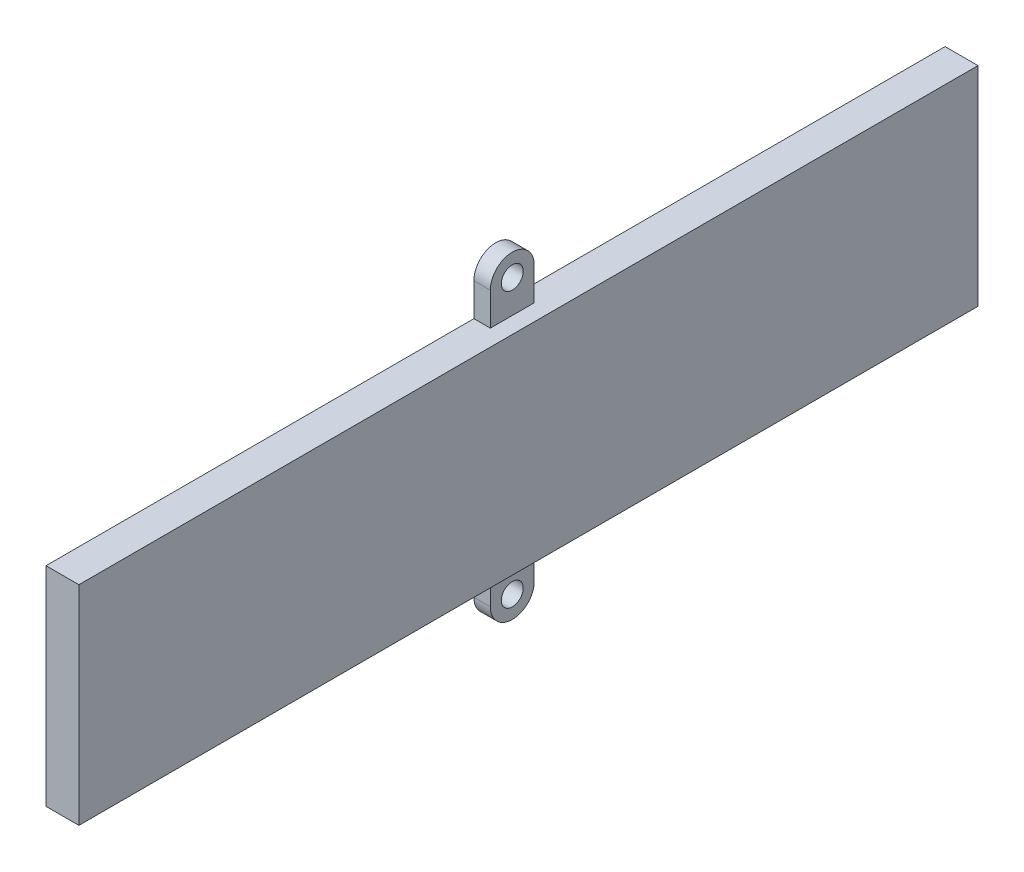
SolidWorks part; units mm, degrees
ref_plane "Alzado" through (0, 0, 0) normal (0, 0, 1) x (1, 0, 0)
ref_plane "Planta" through (0, 0, 0) normal (0, 1, 0) x (1, 0, 0)
ref_plane "Vista lateral" through (0, 0, 0) normal (1, 0, 0) x (0, 0, -1)
sketch "Croquis1" plane through (-42.2573, 0, 0) normal (-1, 0, 0) x (0, 0, 1)
  line L168 (50.1081, 25.9046) -> (54.1081, 25.9046)
  line L169 (50.1081, 6.9046) -> (54.1081, 6.9046)
  line L171 (11.1081, 25.9046) -> (93.1081, 25.9046)
  line L172 (11.1081, 25.9046) -> (11.1081, 6.9046)
  line L173 (11.1081, 6.9046) -> (93.1081, 6.9046)
  line L174 (93.1081, 25.9046) -> (93.1081, 6.9046)
  line L178 (54.1081, 6.9046) -> (54.1081, 3.9046)
  line L179 (50.1081, 3.9046) -> (50.1081, 6.9046)
  line L180 (93.1081, 6.9046) -> (54.1081, 6.9046)
  line L181 (93.1081, 25.9046) -> (93.1081, 6.9046)
  line L182 (54.1081, 25.9046) -> (93.1081, 25.9046)
  line L183 (54.1081, 28.9046) -> (54.1081, 25.9046)
  line L184 (50.1081, 25.9046) -> (50.1081, 28.9046)
  line L185 (11.1081, 25.9046) -> (50.1081, 25.9046)
  line L186 (11.1081, 6.9046) -> (11.1081, 25.9046)
  line L187 (50.1081, 6.9046) -> (11.1081, 6.9046)
  line L188 (54.1081, 6.9046) -> (54.1081, 3.9046)
  line L189 (50.1081, 3.9046) -> (50.1081, 6.9046)
  line L190 (93.1081, 6.9046) -> (54.1081, 6.9046)
  line L191 (93.1081, 25.9046) -> (93.1081, 6.9046)
  line L192 (54.1081, 25.9046) -> (93.1081, 25.9046)
  line L193 (54.1081, 28.9046) -> (54.1081, 25.9046)
  line L194 (50.1081, 25.9046) -> (50.1081, 28.9046)
  line L195 (11.1081, 25.9046) -> (50.1081, 25.9046)
  line L196 (11.1081, 6.9046) -> (11.1081, 25.9046)
  line L197 (50.1081, 6.9046) -> (11.1081, 6.9046)
  arc A28 (50.1081, 28.9046) -> (54.1081, 28.9046) centre (52.1081, 28.9046) cw
  arc A29 (50.1081, 3.9046) -> (54.1081, 3.9046) centre (52.1081, 3.9046) ccw
  arc A30 (50.1081, 3.9046) -> (54.1081, 3.9046) centre (52.1081, 3.9046) ccw
  dimension "D1" = 0.5
extrude "Saliente-Extruir1" add sketch "Croquis1" against normal up to surface (1.5 mm away) contours A28 L194 L168 L193 | L189 A30 L188 L169 region at (-42.2573, 28.2118, 52.1081) region at (-42.2573, 4.5974, 52.1081)
ref_plane "Plano1" through (-42.2573, 26.4046, 10.6081) normal (0, -1, 0) x (-1, 0, 0)
sketch "Croquis4" plane through (-42.2573, 0, 0) normal (-1, 0, 0) x (0, 0, 1)
  line L0 (10.6081, 26.4046) -> (49.6081, 26.4046) construction
  line L1 (11.1581, 25.9046) -> (93.1081, 25.9046)
  line L2 (11.1581, 25.9046) -> (11.1581, 6.9046)
  line L3 (11.1581, 6.9046) -> (93.1081, 6.9046)
  line L4 (93.1081, 25.9046) -> (93.1081, 6.9046)
  line L5 (54.6081, 6.4046) -> (93.6081, 6.4046) construction
  line L6 (10.6081, 26.4046) -> (10.6081, 6.4046) construction
  line L7 (93.6081, 26.4046) -> (93.6081, 6.4046) construction
  dimension "D1" = 0.5
  dimension "D2" = 0.5
  dimension "D3" = 0.55
  dimension "D4" = 0.5
extrude "Saliente-Extruir2" add sketch "Croquis4" against normal blind 3
sketch "Croquis5" plane through (-40.7573, 0, 0) normal (1, 0, 0) x (0, 0, -1)
  circle A0 centre (-52.1081, 28.9046) radius 1
  circle A1 centre (-52.1081, 3.9046) radius 1
extrude "Cortar-Extruir1" cut sketch "Croquis5" against normal blind 3
sketch "Croquis6" plane through (-42.2573, 0, 0) normal (-1, 0, 0) x (0, 0, 1)
  line L4 (27.972, 19.1109) -> (28.6141, 19.1109)
  line L5 (28.6141, 19.1109) -> (28.6141, 15.5831)
  line L6 (28.6141, 15.5831) -> (28.6225, 15.3461)
  line L7 (28.6225, 15.3461) -> (28.6477, 15.1286)
  line L8 (28.6477, 15.1286) -> (28.6666, 15.0269)
  line L9 (28.6666, 15.0269) -> (28.6896, 14.9299)
  line L10 (28.6896, 14.9299) -> (28.7167, 14.8374)
  line L11 (28.7167, 14.8374) -> (28.7479, 14.7495)
  line L12 (28.7479, 14.7495) -> (28.7832, 14.666)
  line L13 (28.7832, 14.666) -> (28.8225, 14.5868)
  line L14 (28.8225, 14.5868) -> (28.8659, 14.5119)
  line L15 (28.8659, 14.5119) -> (28.9133, 14.4412)
  line L16 (28.9133, 14.4412) -> (28.9646, 14.3747)
  line L17 (28.9646, 14.3747) -> (29.0199, 14.3123)
  line L18 (29.0199, 14.3123) -> (29.0792, 14.2538)
  line L19 (29.0792, 14.2538) -> (29.1424, 14.1993)
  line L20 (29.1424, 14.1993) -> (29.2095, 14.1486)
  line L21 (29.2095, 14.1486) -> (29.2805, 14.1018)
  line L22 (29.2805, 14.1018) -> (29.3553, 14.0586)
  line L23 (29.3553, 14.0586) -> (29.434, 14.0191)
  line L24 (29.434, 14.0191) -> (29.6029, 13.9507)
  line L25 (29.6029, 13.9507) -> (29.7868, 13.896)
  line L26 (29.7868, 13.896) -> (29.9857, 13.8545)
  line L27 (29.9857, 13.8545) -> (30.1994, 13.8255)
  line L28 (30.1994, 13.8255) -> (30.4277, 13.8086)
  line L29 (30.4277, 13.8086) -> (30.6704, 13.803)
  line L30 (30.6704, 13.803) -> (30.9971, 13.8117)
  line L31 (30.9971, 13.8117) -> (31.1455, 13.8225)
  line L32 (31.1455, 13.8225) -> (31.2845, 13.8374)
  line L33 (31.2845, 13.8374) -> (31.4145, 13.8565)
  line L34 (31.4145, 13.8565) -> (31.5359, 13.8797)
  line L35 (31.5359, 13.8797) -> (31.6491, 13.9069)
  line L36 (31.6491, 13.9069) -> (31.7546, 13.9381)
  line L37 (31.7546, 13.9381) -> (31.8527, 13.9732)
  line L38 (31.8527, 13.9732) -> (31.9439, 14.0121)
  line L39 (31.9439, 14.0121) -> (32.0287, 14.0549)
  line L40 (32.0287, 14.0549) -> (32.1073, 14.1013)
  line L41 (32.1073, 14.1013) -> (32.1803, 14.1514)
  line L42 (32.1803, 14.1514) -> (32.248, 14.2052)
  line L43 (32.248, 14.2052) -> (32.3109, 14.2625)
  line L44 (32.3109, 14.2625) -> (32.3694, 14.3233)
  line L45 (32.3694, 14.3233) -> (32.4198, 14.3825)
  line L46 (32.4198, 14.3825) -> (32.4647, 14.4442)
  line L47 (32.4647, 14.4442) -> (32.5043, 14.5082)
  line L48 (32.5043, 14.5082) -> (32.539, 14.5744)
  line L49 (32.539, 14.5744) -> (32.5947, 14.7123)
  line L50 (32.5947, 14.7123) -> (32.6346, 14.8567)
  line L51 (32.6346, 14.8567) -> (32.6611, 15.006)
  line L52 (32.6611, 15.006) -> (32.6769, 15.1588)
  line L53 (32.6769, 15.1588) -> (32.6844, 15.3138)
  line L54 (32.6844, 15.3138) -> (32.6864, 15.4694)
  line L55 (32.6864, 15.4694) -> (32.6864, 18.8101)
  line L56 (32.6864, 18.8101) -> (32.6895, 18.8697)
  line L57 (32.6895, 18.8697) -> (32.6995, 18.9257)
  line L58 (32.6995, 18.9257) -> (32.7168, 18.9767)
  line L59 (32.7168, 18.9767) -> (32.7422, 19.0215)
  line L60 (32.7422, 19.0215) -> (32.7765, 19.0586)
  line L61 (32.7765, 19.0586) -> (32.8201, 19.0868)
  line L62 (32.8201, 19.0868) -> (32.8739, 19.1046)
  line L63 (32.8739, 19.1046) -> (32.9384, 19.1109)
  line L64 (32.9384, 19.1109) -> (33.4261, 19.1109)
  line L65 (33.4261, 19.1109) -> (33.4261, 19.3548)
  line L66 (33.4261, 19.3548) -> (31.7108, 19.3548)
  line L67 (31.7108, 19.3548) -> (31.7108, 19.1109)
  line L68 (31.7108, 19.1109) -> (32.0766, 19.1109)
  line L69 (32.0766, 19.1109) -> (32.1601, 19.1046)
  line L70 (32.1601, 19.1046) -> (32.2333, 19.0868)
  line L71 (32.2333, 19.0868) -> (32.296, 19.0586)
  line L72 (32.296, 19.0586) -> (32.348, 19.0215)
  line L73 (32.348, 19.0215) -> (32.3889, 18.9767)
  line L74 (32.3889, 18.9767) -> (32.4184, 18.9257)
  line L75 (32.4184, 18.9257) -> (32.4364, 18.8697)
  line L76 (32.4364, 18.8697) -> (32.4424, 18.8101)
  line L77 (32.4424, 18.8101) -> (32.4424, 16.0791)
  line L78 (32.4424, 16.0791) -> (32.4395, 15.5927)
  line L79 (32.4395, 15.5927) -> (32.4326, 15.3665)
  line L80 (32.4326, 15.3665) -> (32.4191, 15.1574)
  line L81 (32.4191, 15.1574) -> (32.3968, 14.9702)
  line L82 (32.3968, 14.9702) -> (32.3636, 14.8091)
  line L83 (32.3636, 14.8091) -> (32.3422, 14.7397)
  line L84 (32.3422, 14.7397) -> (32.3173, 14.6786)
  line L85 (32.3173, 14.6786) -> (32.2885, 14.6263)
  line L86 (32.2885, 14.6263) -> (32.2556, 14.5834)
  line L87 (32.2556, 14.5834) -> (32.1826, 14.4923)
  line L88 (32.1826, 14.4923) -> (32.091, 14.3989)
  line L89 (32.091, 14.3989) -> (31.9796, 14.3078)
  line L90 (31.9796, 14.3078) -> (31.9161, 14.2646)
  line L91 (31.9161, 14.2646) -> (31.8472, 14.2236)
  line L92 (31.8472, 14.2236) -> (31.7728, 14.1855)
  line L93 (31.7728, 14.1855) -> (31.6927, 14.1509)
  line L94 (31.6927, 14.1509) -> (31.6068, 14.1202)
  line L95 (31.6068, 14.1202) -> (31.5149, 14.0941)
  line L96 (31.5149, 14.0941) -> (31.4169, 14.0732)
  line L97 (31.4169, 14.0732) -> (31.3127, 14.058)
  line L98 (31.3127, 14.058) -> (31.2021, 14.049)
  line L99 (31.2021, 14.049) -> (31.085, 14.047)
  line L100 (31.085, 14.047) -> (30.9212, 14.0528)
  line L101 (30.9212, 14.0528) -> (30.7738, 14.0672)
  line L102 (30.7738, 14.0672) -> (30.6419, 14.0901)
  line L103 (30.6419, 14.0901) -> (30.5248, 14.1217)
  line L104 (30.5248, 14.1217) -> (30.4217, 14.162)
  line L105 (30.4217, 14.162) -> (30.3316, 14.2108)
  line L106 (30.3316, 14.2108) -> (30.254, 14.2683)
  line L107 (30.254, 14.2683) -> (30.1879, 14.3344)
  line L108 (30.1879, 14.3344) -> (30.1326, 14.4093)
  line L109 (30.1326, 14.4093) -> (30.0872, 14.4928)
  line L110 (30.0872, 14.4928) -> (30.051, 14.5849)
  line L111 (30.051, 14.5849) -> (30.0231, 14.6858)
  line L112 (30.0231, 14.6858) -> (30.0029, 14.7954)
  line L113 (30.0029, 14.7954) -> (29.9894, 14.9138)
  line L114 (29.9894, 14.9138) -> (29.9819, 15.0408)
  line L115 (29.9819, 15.0408) -> (29.9796, 15.1767)
  line L116 (29.9796, 15.1767) -> (29.9796, 19.1109)
  line L117 (29.9796, 19.1109) -> (30.6623, 19.1109)
  line L118 (30.6623, 19.1109) -> (30.6623, 19.3548)
  line L119 (30.6623, 19.3548) -> (27.972, 19.3548)
  line L120 (27.972, 19.3548) -> (27.972, 19.1109)
  line L121 (19.4343, 21.6816) -> (22.1885, 18.3616)
  line L122 (22.1885, 18.3616) -> (22.3112, 18.1954)
  line L123 (22.3112, 18.1954) -> (22.4201, 18.0189)
  line L124 (22.4201, 18.0189) -> (22.5144, 17.833)
  line L125 (22.5144, 17.833) -> (22.5933, 17.6384)
  line L126 (22.5933, 17.6384) -> (22.6561, 17.4361)
  line L127 (22.6561, 17.4361) -> (22.7018, 17.2267)
  line L128 (22.7018, 17.2267) -> (22.7299, 17.0111)
  line L129 (22.7299, 17.0111) -> (22.737, 16.9012)
  line L130 (22.737, 16.9012) -> (22.7394, 16.79)
  line L131 (22.7394, 16.79) -> (22.7362, 16.6618)
  line L132 (22.7362, 16.6618) -> (22.7266, 16.5352)
  line L133 (22.7266, 16.5352) -> (22.7109, 16.4104)
  line L134 (22.7109, 16.4104) -> (22.6892, 16.2877)
  line L135 (22.6892, 16.2877) -> (22.6617, 16.167)
  line L136 (22.6617, 16.167) -> (22.6284, 16.0488)
  line L137 (22.6284, 16.0488) -> (22.5896, 15.9329)
  line L138 (22.5896, 15.9329) -> (22.5454, 15.8197)
  line L139 (22.5454, 15.8197) -> (22.496, 15.7093)
  line L140 (22.496, 15.7093) -> (22.4415, 15.6018)
  line L141 (22.4415, 15.6018) -> (22.3821, 15.4974)
  line L142 (22.3821, 15.4974) -> (22.3179, 15.3962)
  line L143 (22.3179, 15.3962) -> (22.2491, 15.2985)
  line L144 (22.2491, 15.2985) -> (22.1758, 15.2043)
  line L145 (22.1758, 15.2043) -> (22.0982, 15.1139)
  line L146 (22.0982, 15.1139) -> (22.0165, 15.0273)
  line L147 (22.0165, 15.0273) -> (21.9308, 14.9447)
  line L148 (21.9308, 14.9447) -> (21.8412, 14.8664)
  line L149 (21.8412, 14.8664) -> (21.748, 14.7923)
  line L150 (21.748, 14.7923) -> (21.6512, 14.7228)
  line L151 (21.6512, 14.7228) -> (21.551, 14.658)
  line L152 (21.551, 14.658) -> (21.4477, 14.5979)
  line L153 (21.4477, 14.5979) -> (21.3412, 14.5429)
  line L154 (21.3412, 14.5429) -> (21.2319, 14.493)
  line L155 (21.2319, 14.493) -> (21.1198, 14.4483)
  line L156 (21.1198, 14.4483) -> (21.0051, 14.4091)
  line L157 (21.0051, 14.4091) -> (20.888, 14.3755)
  line L158 (20.888, 14.3755) -> (20.7686, 14.3477)
  line L159 (20.7686, 14.3477) -> (20.647, 14.3257)
  line L160 (20.647, 14.3257) -> (20.5235, 14.3099)
  line L161 (20.5235, 14.3099) -> (20.3981, 14.3003)
  line L162 (20.3981, 14.3003) -> (20.2711, 14.297)
  line L163 (20.2711, 14.297) -> (20.1077, 14.3027)
  line L164 (20.1077, 14.3027) -> (19.9476, 14.3196)
  line L165 (19.9476, 14.3196) -> (19.7911, 14.3471)
  line L166 (19.7911, 14.3471) -> (19.6385, 14.3849)
  line L167 (19.6385, 14.3849) -> (19.4898, 14.4323)
  line L168 (19.4898, 14.4323) -> (19.3454, 14.4891)
  line L169 (19.3454, 14.4891) -> (19.2054, 14.5546)
  line L170 (19.2054, 14.5546) -> (19.0701, 14.6284)
  line L171 (19.0701, 14.6284) -> (18.9396, 14.7101)
  line L172 (18.9396, 14.7101) -> (18.8143, 14.7992)
  line L173 (18.8143, 14.7992) -> (18.6942, 14.8952)
  line L174 (18.6942, 14.8952) -> (18.5797, 14.9976)
  line L175 (18.5797, 14.9976) -> (18.471, 15.106)
  line L176 (18.471, 15.106) -> (18.3682, 15.2199)
  line L177 (18.3682, 15.2199) -> (18.2716, 15.3388)
  line L178 (18.2716, 15.3388) -> (18.1814, 15.4624)
  line L179 (18.1814, 15.4624) -> (16.7124, 17.2468)
  line L180 (16.7124, 17.2468) -> (16.7124, 18.0118)
  line L181 (16.7124, 18.0118) -> (18.5461, 15.7244)
  line L182 (18.5461, 15.7244) -> (18.5617, 15.6995)
  line L183 (18.5617, 15.6995) -> (18.7273, 15.5167)
  line L184 (18.7273, 15.5167) -> (18.9066, 15.3421)
  line L185 (18.9066, 15.3421) -> (19.0013, 15.2594)
  line L186 (19.0013, 15.2594) -> (19.0995, 15.1806)
  line L187 (19.0995, 15.1806) -> (19.2011, 15.1063)
  line L188 (19.2011, 15.1063) -> (19.3061, 15.0372)
  line L189 (19.3061, 15.0372) -> (19.4146, 14.9739)
  line L190 (19.4146, 14.9739) -> (19.5265, 14.917)
  line L191 (19.5265, 14.917) -> (19.6419, 14.8671)
  line L192 (19.6419, 14.8671) -> (19.7608, 14.8249)
  line L193 (19.7608, 14.8249) -> (19.8831, 14.791)
  line L194 (19.8831, 14.791) -> (20.0089, 14.766)
  line L195 (20.0089, 14.766) -> (20.1382, 14.7506)
  line L196 (20.1382, 14.7506) -> (20.2711, 14.7453)
  line L197 (20.2711, 14.7453) -> (20.3747, 14.7479)
  line L198 (20.3747, 14.7479) -> (20.4769, 14.7558)
  line L199 (20.4769, 14.7558) -> (20.5778, 14.7687)
  line L200 (20.5778, 14.7687) -> (20.677, 14.7866)
  line L201 (20.677, 14.7866) -> (20.7745, 14.8094)
  line L202 (20.7745, 14.8094) -> (20.8703, 14.8368)
  line L203 (20.8703, 14.8368) -> (20.964, 14.8689)
  line L204 (20.964, 14.8689) -> (21.0557, 14.9054)
  line L205 (21.0557, 14.9054) -> (21.1451, 14.9462)
  line L206 (21.1451, 14.9462) -> (21.2322, 14.9912)
  line L207 (21.2322, 14.9912) -> (21.3988, 15.0934)
  line L208 (21.3988, 15.0934) -> (21.5544, 15.2109)
  line L209 (21.5544, 15.2109) -> (21.698, 15.3426)
  line L210 (21.698, 15.3426) -> (21.8286, 15.4877)
  line L211 (21.8286, 15.4877) -> (21.9452, 15.645)
  line L212 (21.9452, 15.645) -> (22.0467, 15.8135)
  line L213 (22.0467, 15.8135) -> (22.0914, 15.9017)
  line L214 (22.0914, 15.9017) -> (22.132, 15.9924)
  line L215 (22.132, 15.9924) -> (22.1683, 16.0853)
  line L216 (22.1683, 16.0853) -> (22.2002, 16.1804)
  line L217 (22.2002, 16.1804) -> (22.2275, 16.2776)
  line L218 (22.2275, 16.2776) -> (22.2501, 16.3768)
  line L219 (22.2501, 16.3768) -> (22.268, 16.4777)
  line L220 (22.268, 16.4777) -> (22.2809, 16.5803)
  line L221 (22.2809, 16.5803) -> (22.2887, 16.6844)
  line L222 (22.2887, 16.6844) -> (22.2914, 16.79)
  line L223 (22.2914, 16.79) -> (22.2836, 16.9709)
  line L224 (22.2836, 16.9709) -> (22.2608, 17.1473)
  line L225 (22.2608, 17.1473) -> (22.2236, 17.3185)
  line L226 (22.2236, 17.3185) -> (22.1726, 17.4839)
  line L227 (22.1726, 17.4839) -> (22.1085, 17.6429)
  line L228 (22.1085, 17.6429) -> (22.032, 17.7947)
  line L229 (22.032, 17.7947) -> (21.9437, 17.9389)
  line L230 (21.9437, 17.9389) -> (21.8442, 18.0746)
  line L231 (21.8442, 18.0746) -> (19.4343, 20.9137)
  line L232 (19.4343, 20.9137) -> (19.4343, 21.6816)
  line L233 (21.6493, 17.6288) -> (21.6993, 17.5345)
  line L234 (21.6993, 17.5345) -> (21.7428, 17.4363)
  line L235 (21.7428, 17.4363) -> (21.7799, 17.3346)
  line L236 (21.7799, 17.3346) -> (21.8104, 17.2295)
  line L237 (21.8104, 17.2295) -> (21.8343, 17.1216)
  line L238 (21.8343, 17.1216) -> (21.8514, 17.0112)
  line L239 (21.8514, 17.0112) -> (21.8617, 16.8987)
  line L240 (21.8617, 16.8987) -> (21.8652, 16.7843)
  line L241 (21.8652, 16.7843) -> (21.857, 16.6167)
  line L242 (21.857, 16.6167) -> (21.833, 16.4538)
  line L243 (21.833, 16.4538) -> (21.794, 16.2967)
  line L244 (21.794, 16.2967) -> (21.7408, 16.146)
  line L245 (21.7408, 16.146) -> (21.6741, 16.0026)
  line L246 (21.6741, 16.0026) -> (21.5948, 15.8674)
  line L247 (21.5948, 15.8674) -> (21.5037, 15.7411)
  line L248 (21.5037, 15.7411) -> (21.4015, 15.6247)
  line L249 (21.4015, 15.6247) -> (21.2891, 15.5188)
  line L250 (21.2891, 15.5188) -> (21.1672, 15.4244)
  line L251 (21.1672, 15.4244) -> (21.0367, 15.3422)
  line L252 (21.0367, 15.3422) -> (20.8983, 15.2732)
  line L253 (20.8983, 15.2732) -> (20.7528, 15.218)
  line L254 (20.7528, 15.218) -> (20.6011, 15.1776)
  line L255 (20.6011, 15.1776) -> (20.4439, 15.1527)
  line L256 (20.4439, 15.1527) -> (20.282, 15.1443)
  line L257 (20.282, 15.1443) -> (20.1805, 15.1476)
  line L258 (20.1805, 15.1476) -> (20.0807, 15.1574)
  line L259 (20.0807, 15.1574) -> (19.9828, 15.1735)
  line L260 (19.9828, 15.1735) -> (19.887, 15.1957)
  line L261 (19.887, 15.1957) -> (19.7934, 15.2238)
  line L262 (19.7934, 15.2238) -> (19.7024, 15.2577)
  line L263 (19.7024, 15.2577) -> (19.614, 15.297)
  line L264 (19.614, 15.297) -> (19.5285, 15.3416)
  line L265 (19.5285, 15.3416) -> (19.446, 15.3913)
  line L266 (19.446, 15.3913) -> (19.3668, 15.4459)
  line L267 (19.3668, 15.4459) -> (19.2911, 15.5052)
  line L268 (19.2911, 15.5052) -> (19.219, 15.569)
  line L269 (19.219, 15.569) -> (19.1507, 15.6371)
  line L270 (19.1507, 15.6371) -> (19.0864, 15.7093)
  line L271 (19.0864, 15.7093) -> (19.0264, 15.7853)
  line L272 (19.0264, 15.7853) -> (18.9707, 15.8651)
  line L273 (18.9707, 15.8651) -> (16.7124, 18.6246)
  line L274 (16.7124, 18.6246) -> (16.7124, 19.3898)
  line L275 (16.7124, 19.3898) -> (19.4043, 16.097)
  line L276 (19.4043, 16.097) -> (19.4931, 15.982)
  line L277 (19.4931, 15.982) -> (19.5807, 15.8903)
  line L278 (19.5807, 15.8903) -> (19.6703, 15.8185)
  line L279 (19.6703, 15.8185) -> (19.7653, 15.7633)
  line L280 (19.7653, 15.7633) -> (19.8687, 15.7212)
  line L281 (19.8687, 15.7212) -> (19.9838, 15.6889)
  line L282 (19.9838, 15.6889) -> (20.1139, 15.663)
  line L283 (20.1139, 15.663) -> (20.2621, 15.6402)
  line L284 (20.2621, 15.6402) -> (20.3759, 15.6319)
  line L285 (20.3759, 15.6319) -> (20.4867, 15.639)
  line L286 (20.4867, 15.639) -> (20.5938, 15.6604)
  line L287 (20.5938, 15.6604) -> (20.6966, 15.6954)
  line L288 (20.6966, 15.6954) -> (20.7946, 15.7427)
  line L289 (20.7946, 15.7427) -> (20.8873, 15.8016)
  line L290 (20.8873, 15.8016) -> (20.9738, 15.8711)
  line L291 (20.9738, 15.8711) -> (21.0538, 15.95)
  line L292 (21.0538, 15.95) -> (21.1266, 16.0376)
  line L293 (21.1266, 16.0376) -> (21.1916, 16.1328)
  line L294 (21.1916, 16.1328) -> (21.2483, 16.2346)
  line L295 (21.2483, 16.2346) -> (21.2959, 16.3421)
  line L296 (21.2959, 16.3421) -> (21.334, 16.4543)
  line L297 (21.334, 16.4543) -> (21.362, 16.5703)
  line L298 (21.362, 16.5703) -> (21.3792, 16.689)
  line L299 (21.3792, 16.689) -> (21.385, 16.8095)
  line L300 (21.385, 16.8095) -> (21.3806, 16.9614)
  line L301 (21.3806, 16.9614) -> (21.3639, 17.1041)
  line L302 (21.3639, 17.1041) -> (21.3494, 17.1726)
  line L303 (21.3494, 17.1726) -> (21.3299, 17.2394)
  line L304 (21.3299, 17.2394) -> (21.3048, 17.3048)
  line L305 (21.3048, 17.3048) -> (21.2734, 17.3691)
  line L306 (21.2734, 17.3691) -> (19.4343, 19.5605)
  line L307 (19.4343, 19.5605) -> (19.4343, 20.3283)
  line L308 (19.4343, 20.3283) -> (21.6493, 17.6288)
  line L309 (20.8854, 17.2656) -> (20.9267, 16.9801)
  line L310 (20.9267, 16.9801) -> (20.8442, 16.5564)
  line L311 (20.8442, 16.5564) -> (20.7935, 16.3357)
  line L312 (20.7935, 16.3357) -> (20.7507, 16.1815)
  line L313 (20.7507, 16.1815) -> (20.7306, 16.1274)
  line L314 (20.7306, 16.1274) -> (20.7134, 16.1016)
  line L315 (20.7134, 16.1016) -> (20.609, 16.0515)
  line L316 (20.609, 16.0515) -> (20.509, 16.0175)
  line L317 (20.509, 16.0175) -> (20.4138, 15.998)
  line L318 (20.4138, 15.998) -> (20.3236, 15.991)
  line L319 (20.3236, 15.991) -> (20.2388, 15.9949)
  line L320 (20.2388, 15.9949) -> (20.1596, 16.0078)
  line L321 (20.1596, 16.0078) -> (20.0864, 16.0279)
  line L322 (20.0864, 16.0279) -> (20.0195, 16.0535)
  line L323 (20.0195, 16.0535) -> (19.9055, 16.114)
  line L324 (19.9055, 16.114) -> (19.8201, 16.175)
  line L325 (19.8201, 16.175) -> (19.7656, 16.2223)
  line L326 (19.7656, 16.2223) -> (19.7445, 16.2416)
  line L327 (19.7445, 16.2416) -> (19.813, 16.1997)
  line L328 (19.813, 16.1997) -> (19.8875, 16.1685)
  line L329 (19.8875, 16.1685) -> (19.9671, 16.149)
  line L330 (19.9671, 16.149) -> (20.0508, 16.1423)
  line L331 (20.0508, 16.1423) -> (20.1054, 16.1451)
  line L332 (20.1054, 16.1451) -> (20.1585, 16.1534)
  line L333 (20.1585, 16.1534) -> (20.2097, 16.167)
  line L334 (20.2097, 16.167) -> (20.2587, 16.1855)
  line L335 (20.2587, 16.1855) -> (20.3054, 16.2087)
  line L336 (20.3054, 16.2087) -> (20.3495, 16.2362)
  line L337 (20.3495, 16.2362) -> (20.3906, 16.2679)
  line L338 (20.3906, 16.2679) -> (20.4285, 16.3034)
  line L339 (20.4285, 16.3034) -> (20.463, 16.3425)
  line L340 (20.463, 16.3425) -> (20.4938, 16.3848)
  line L341 (20.4938, 16.3848) -> (20.5205, 16.4302)
  line L342 (20.5205, 16.4302) -> (20.543, 16.4783)
  line L343 (20.543, 16.4783) -> (20.561, 16.5289)
  line L344 (20.561, 16.5289) -> (20.5741, 16.5816)
  line L345 (20.5741, 16.5816) -> (20.5822, 16.6362)
  line L346 (20.5822, 16.6362) -> (20.585, 16.6925)
  line L347 (20.585, 16.6925) -> (20.5825, 16.7455)
  line L348 (20.5825, 16.7455) -> (20.5753, 16.797)
  line L349 (20.5753, 16.797) -> (20.5475, 16.8947)
  line L350 (20.5475, 16.8947) -> (20.5033, 16.984)
  line L351 (20.5033, 16.984) -> (20.4445, 17.0631)
  line L352 (20.4445, 17.0631) -> (19.4343, 18.2593)
  line L353 (19.4343, 18.2593) -> (19.4343, 19.0269)
  line L354 (19.4343, 19.0269) -> (20.8854, 17.2656)
  line L355 (17.829, 14.5352) -> (16.7124, 15.8936)
  line L356 (16.7124, 15.8936) -> (16.7124, 16.6586)
  line L357 (16.7124, 16.6586) -> (17.985, 15.071)
  line L358 (17.985, 15.071) -> (18.0605, 14.9833)
  line L359 (18.0605, 14.9833) -> (18.1436, 14.8877)
  line L360 (18.1436, 14.8877) -> (18.2566, 14.7682)
  line L361 (18.2566, 14.7682) -> (18.399, 14.6326)
  line L362 (18.399, 14.6326) -> (18.5705, 14.4891)
  line L363 (18.5705, 14.4891) -> (18.6671, 14.4168)
  line L364 (18.6671, 14.4168) -> (18.7709, 14.3454)
  line L365 (18.7709, 14.3454) -> (18.8817, 14.2761)
  line L366 (18.8817, 14.2761) -> (18.9997, 14.2097)
  line L367 (18.9997, 14.2097) -> (19.1247, 14.1473)
  line L368 (19.1247, 14.1473) -> (19.2567, 14.0898)
  line L369 (19.2567, 14.0898) -> (19.3956, 14.0383)
  line L370 (19.3956, 14.0383) -> (19.5415, 13.9938)
  line L371 (19.5415, 13.9938) -> (19.6942, 13.9571)
  line L372 (19.6942, 13.9571) -> (19.8537, 13.9294)
  line L373 (19.8537, 13.9294) -> (20.0201, 13.9117)
  line L374 (20.0201, 13.9117) -> (20.1932, 13.9048)
  line L375 (20.1932, 13.9048) -> (20.373, 13.9099)
  line L376 (20.373, 13.9099) -> (20.5594, 13.9279)
  line L377 (20.5594, 13.9279) -> (20.7525, 13.9598)
  line L378 (20.7525, 13.9598) -> (20.9521, 14.0066)
  line L379 (20.9521, 14.0066) -> (21.1583, 14.0693)
  line L380 (21.1583, 14.0693) -> (21.371, 14.1488)
  line L381 (21.371, 14.1488) -> (21.5902, 14.2463)
  line L382 (21.5902, 14.2463) -> (21.8157, 14.3626)
  line L383 (21.8157, 14.3626) -> (21.7398, 14.2879)
  line L384 (21.7398, 14.2879) -> (21.6565, 14.2156)
  line L385 (21.6565, 14.2156) -> (21.5659, 14.146)
  line L386 (21.5659, 14.146) -> (21.4686, 14.0793)
  line L387 (21.4686, 14.0793) -> (21.365, 14.0161)
  line L388 (21.365, 14.0161) -> (21.2553, 13.9566)
  line L389 (21.2553, 13.9566) -> (21.14, 13.9011)
  line L390 (21.14, 13.9011) -> (21.0194, 13.85)
  line L391 (21.0194, 13.85) -> (20.8939, 13.8037)
  line L392 (20.8939, 13.8037) -> (20.7639, 13.7624)
  line L393 (20.7639, 13.7624) -> (20.6297, 13.7266)
  line L394 (20.6297, 13.7266) -> (20.4917, 13.6965)
  line L395 (20.4917, 13.6965) -> (20.3503, 13.6725)
  line L396 (20.3503, 13.6725) -> (20.2059, 13.6549)
  line L397 (20.2059, 13.6549) -> (20.0588, 13.6442)
  line L398 (20.0588, 13.6442) -> (19.9095, 13.6405)
  line L399 (19.9095, 13.6405) -> (19.734, 13.6456)
  line L400 (19.734, 13.6456) -> (19.563, 13.6606)
  line L401 (19.563, 13.6606) -> (19.3967, 13.6847)
  line L402 (19.3967, 13.6847) -> (19.2355, 13.7173)
  line L403 (19.2355, 13.7173) -> (19.0798, 13.7578)
  line L404 (19.0798, 13.7578) -> (18.9299, 13.8055)
  line L405 (18.9299, 13.8055) -> (18.7862, 13.8597)
  line L406 (18.7862, 13.8597) -> (18.649, 13.9199)
  line L407 (18.649, 13.9199) -> (18.5187, 13.9853)
  line L408 (18.5187, 13.9853) -> (18.3957, 14.0552)
  line L409 (18.3957, 14.0552) -> (18.2802, 14.1292)
  line L410 (18.2802, 14.1292) -> (18.1727, 14.2064)
  line L411 (18.1727, 14.2064) -> (18.0734, 14.2863)
  line L412 (18.0734, 14.2863) -> (17.9828, 14.3682)
  line L413 (17.9828, 14.3682) -> (17.9012, 14.4514)
  line L414 (17.9012, 14.4514) -> (17.829, 14.5352)
  line L415 (23.8929, 21.6816) -> (21.1385, 18.3616)
  line L416 (21.1385, 18.3616) -> (21.0157, 18.1954)
  line L417 (21.0157, 18.1954) -> (20.9068, 18.0189)
  line L418 (20.9068, 18.0189) -> (20.8126, 17.833)
  line L419 (20.8126, 17.833) -> (20.7337, 17.6384)
  line L420 (20.7337, 17.6384) -> (20.6709, 17.4361)
  line L421 (20.6709, 17.4361) -> (20.6252, 17.2267)
  line L422 (20.6252, 17.2267) -> (20.5971, 17.0111)
  line L423 (20.5971, 17.0111) -> (20.59, 16.9012)
  line L424 (20.59, 16.9012) -> (20.5876, 16.79)
  line L425 (20.5876, 16.79) -> (20.5908, 16.6618)
  line L426 (20.5908, 16.6618) -> (20.6004, 16.5352)
  line L427 (20.6004, 16.5352) -> (20.6161, 16.4104)
  line L428 (20.6161, 16.4104) -> (20.6378, 16.2877)
  line L429 (20.6378, 16.2877) -> (20.6653, 16.167)
  line L430 (20.6653, 16.167) -> (20.6986, 16.0488)
  line L431 (20.6986, 16.0488) -> (20.7374, 15.9329)
  line L432 (20.7374, 15.9329) -> (20.7816, 15.8197)
  line L433 (20.7816, 15.8197) -> (20.831, 15.7093)
  line L434 (20.831, 15.7093) -> (20.8856, 15.6018)
  line L435 (20.8856, 15.6018) -> (20.945, 15.4974)
  line L436 (20.945, 15.4974) -> (21.0092, 15.3962)
  line L437 (21.0092, 15.3962) -> (21.078, 15.2985)
  line L438 (21.078, 15.2985) -> (21.1513, 15.2043)
  line L439 (21.1513, 15.2043) -> (21.2289, 15.1139)
  line L440 (21.2289, 15.1139) -> (21.3106, 15.0273)
  line L441 (21.3106, 15.0273) -> (21.3964, 14.9447)
  line L442 (21.3964, 14.9447) -> (21.4859, 14.8664)
  line L443 (21.4859, 14.8664) -> (21.5792, 14.7923)
  line L444 (21.5792, 14.7923) -> (21.676, 14.7228)
  line L445 (21.676, 14.7228) -> (21.7761, 14.658)
  line L446 (21.7761, 14.658) -> (21.8795, 14.5979)
  line L447 (21.8795, 14.5979) -> (21.9859, 14.5429)
  line L448 (21.9859, 14.5429) -> (22.0953, 14.493)
  line L449 (22.0953, 14.493) -> (22.2074, 14.4483)
  line L450 (22.2074, 14.4483) -> (22.3221, 14.4091)
  line L451 (22.3221, 14.4091) -> (22.4392, 14.3755)
  line L452 (22.4392, 14.3755) -> (22.5586, 14.3477)
  line L453 (22.5586, 14.3477) -> (22.6802, 14.3257)
  line L454 (22.6802, 14.3257) -> (22.8037, 14.3099)
  line L455 (22.8037, 14.3099) -> (22.9291, 14.3003)
  line L456 (22.9291, 14.3003) -> (23.0561, 14.297)
  line L457 (23.0561, 14.297) -> (23.2195, 14.3027)
  line L458 (23.2195, 14.3027) -> (23.3795, 14.3196)
  line L459 (23.3795, 14.3196) -> (23.536, 14.3471)
  line L460 (23.536, 14.3471) -> (23.6886, 14.3849)
  line L461 (23.6886, 14.3849) -> (23.8373, 14.4323)
  line L462 (23.8373, 14.4323) -> (23.9817, 14.4891)
  line L463 (23.9817, 14.4891) -> (24.1217, 14.5546)
  line L464 (24.1217, 14.5546) -> (24.257, 14.6284)
  line L465 (24.257, 14.6284) -> (24.3874, 14.7101)
  line L466 (24.3874, 14.7101) -> (24.5127, 14.7992)
  line L467 (24.5127, 14.7992) -> (24.6328, 14.8952)
  line L468 (24.6328, 14.8952) -> (24.7473, 14.9976)
  line L469 (24.7473, 14.9976) -> (24.856, 15.106)
  line L470 (24.856, 15.106) -> (24.9588, 15.2199)
  line L471 (24.9588, 15.2199) -> (25.0554, 15.3388)
  line L472 (25.0554, 15.3388) -> (25.1456, 15.4624)
  line L473 (25.1456, 15.4624) -> (26.6146, 17.2468)
  line L474 (26.6146, 17.2468) -> (26.6146, 18.0118)
  line L475 (26.6146, 18.0118) -> (24.7809, 15.7244)
  line L476 (24.7809, 15.7244) -> (24.7656, 15.6995)
  line L477 (24.7656, 15.6995) -> (24.5998, 15.5167)
  line L478 (24.5998, 15.5167) -> (24.4205, 15.3421)
  line L479 (24.4205, 15.3421) -> (24.3258, 15.2594)
  line L480 (24.3258, 15.2594) -> (24.2276, 15.1806)
  line L481 (24.2276, 15.1806) -> (24.126, 15.1063)
  line L482 (24.126, 15.1063) -> (24.0209, 15.0372)
  line L483 (24.0209, 15.0372) -> (23.9125, 14.9739)
  line L484 (23.9125, 14.9739) -> (23.8006, 14.917)
  line L485 (23.8006, 14.917) -> (23.6852, 14.8671)
  line L486 (23.6852, 14.8671) -> (23.5663, 14.8249)
  line L487 (23.5663, 14.8249) -> (23.444, 14.791)
  line L488 (23.444, 14.791) -> (23.3182, 14.766)
  line L489 (23.3182, 14.766) -> (23.1889, 14.7506)
  line L490 (23.1889, 14.7506) -> (23.0561, 14.7453)
  line L491 (23.0561, 14.7453) -> (22.9525, 14.7479)
  line L492 (22.9525, 14.7479) -> (22.8502, 14.7558)
  line L493 (22.8502, 14.7558) -> (22.7494, 14.7687)
  line L494 (22.7494, 14.7687) -> (22.6501, 14.7866)
  line L495 (22.6501, 14.7866) -> (22.5526, 14.8094)
  line L496 (22.5526, 14.8094) -> (22.4568, 14.8368)
  line L497 (22.4568, 14.8368) -> (22.3631, 14.8689)
  line L498 (22.3631, 14.8689) -> (22.2714, 14.9054)
  line L499 (22.2714, 14.9054) -> (22.182, 14.9462)
  line L500 (22.182, 14.9462) -> (22.0949, 14.9912)
  line L501 (22.0949, 14.9912) -> (21.9283, 15.0934)
  line L502 (21.9283, 15.0934) -> (21.7726, 15.2109)
  line L503 (21.7726, 15.2109) -> (21.629, 15.3426)
  line L504 (21.629, 15.3426) -> (21.4984, 15.4877)
  line L505 (21.4984, 15.4877) -> (21.3818, 15.645)
  line L506 (21.3818, 15.645) -> (21.2803, 15.8135)
  line L507 (21.2803, 15.8135) -> (21.2356, 15.9017)
  line L508 (21.2356, 15.9017) -> (21.195, 15.9924)
  line L509 (21.195, 15.9924) -> (21.1587, 16.0853)
  line L510 (21.1587, 16.0853) -> (21.1268, 16.1804)
  line L511 (21.1268, 16.1804) -> (21.0995, 16.2776)
  line L512 (21.0995, 16.2776) -> (21.0769, 16.3768)
  line L513 (21.0769, 16.3768) -> (21.059, 16.4777)
  line L514 (21.059, 16.4777) -> (21.0461, 16.5803)
  line L515 (21.0461, 16.5803) -> (21.0383, 16.6844)
  line L516 (21.0383, 16.6844) -> (21.0356, 16.79)
  line L517 (21.0356, 16.79) -> (21.0434, 16.9709)
  line L518 (21.0434, 16.9709) -> (21.0662, 17.1473)
  line L519 (21.0662, 17.1473) -> (21.1034, 17.3185)
  line L520 (21.1034, 17.3185) -> (21.1544, 17.4839)
  line L521 (21.1544, 17.4839) -> (21.2184, 17.6429)
  line L522 (21.2184, 17.6429) -> (21.295, 17.7947)
  line L523 (21.295, 17.7947) -> (21.3833, 17.9389)
  line L524 (21.3833, 17.9389) -> (21.4828, 18.0746)
  line L525 (21.4828, 18.0746) -> (23.8929, 20.9137)
  line L526 (23.8929, 20.9137) -> (23.8929, 21.6816)
  line L527 (21.6777, 17.6288) -> (21.6278, 17.5345)
  line L528 (21.6278, 17.5345) -> (21.5843, 17.4363)
  line L529 (21.5843, 17.4363) -> (21.5472, 17.3346)
  line L530 (21.5472, 17.3346) -> (21.5167, 17.2295)
  line L531 (21.5167, 17.2295) -> (21.4928, 17.1216)
  line L532 (21.4928, 17.1216) -> (21.4756, 17.0112)
  line L533 (21.4756, 17.0112) -> (21.4653, 16.8987)
  line L534 (21.4653, 16.8987) -> (21.4618, 16.7843)
  line L535 (21.4618, 16.7843) -> (21.47, 16.6167)
  line L536 (21.47, 16.6167) -> (21.4939, 16.4538)
  line L537 (21.4939, 16.4538) -> (21.533, 16.2967)
  line L538 (21.533, 16.2967) -> (21.5862, 16.146)
  line L539 (21.5862, 16.146) -> (21.6529, 16.0026)
  line L540 (21.6529, 16.0026) -> (21.7322, 15.8674)
  line L541 (21.7322, 15.8674) -> (21.8233, 15.7411)
  line L542 (21.8233, 15.7411) -> (21.9255, 15.6247)
  line L543 (21.9255, 15.6247) -> (22.0379, 15.5188)
  line L544 (22.0379, 15.5188) -> (22.1598, 15.4244)
  line L545 (22.1598, 15.4244) -> (22.2903, 15.3422)
  line L546 (22.2903, 15.3422) -> (22.4287, 15.2732)
  line L547 (22.4287, 15.2732) -> (22.5742, 15.218)
  line L548 (22.5742, 15.218) -> (22.7259, 15.1776)
  line L549 (22.7259, 15.1776) -> (22.8831, 15.1527)
  line L550 (22.8831, 15.1527) -> (23.045, 15.1443)
  line L551 (23.045, 15.1443) -> (23.1465, 15.1476)
  line L552 (23.1465, 15.1476) -> (23.2463, 15.1574)
  line L553 (23.2463, 15.1574) -> (23.3442, 15.1735)
  line L554 (23.3442, 15.1735) -> (23.44, 15.1957)
  line L555 (23.44, 15.1957) -> (23.5335, 15.2238)
  line L556 (23.5335, 15.2238) -> (23.6246, 15.2577)
  line L557 (23.6246, 15.2577) -> (23.713, 15.297)
  line L558 (23.713, 15.297) -> (23.7985, 15.3416)
  line L559 (23.7985, 15.3416) -> (23.8809, 15.3913)
  line L560 (23.8809, 15.3913) -> (23.9601, 15.4459)
  line L561 (23.9601, 15.4459) -> (24.0359, 15.5052)
  line L562 (24.0359, 15.5052) -> (24.108, 15.569)
  line L563 (24.108, 15.569) -> (24.1763, 15.6371)
  line L564 (24.1763, 15.6371) -> (24.2406, 15.7093)
  line L565 (24.2406, 15.7093) -> (24.3006, 15.7853)
  line L566 (24.3006, 15.7853) -> (24.3562, 15.8651)
  line L567 (24.3562, 15.8651) -> (26.6146, 18.6246)
  line L568 (26.6146, 18.6246) -> (26.6146, 19.3898)
  line L569 (26.6146, 19.3898) -> (23.9227, 16.097)
  line L570 (23.9227, 16.097) -> (23.8339, 15.982)
  line L571 (23.8339, 15.982) -> (23.7463, 15.8903)
  line L572 (23.7463, 15.8903) -> (23.6567, 15.8185)
  line L573 (23.6567, 15.8185) -> (23.5618, 15.7633)
  line L574 (23.5618, 15.7633) -> (23.4584, 15.7212)
  line L575 (23.4584, 15.7212) -> (23.3433, 15.6889)
  line L576 (23.3433, 15.6889) -> (23.2133, 15.663)
  line L577 (23.2133, 15.663) -> (23.0651, 15.6402)
  line L578 (23.0651, 15.6402) -> (22.9513, 15.6319)
  line L579 (22.9513, 15.6319) -> (22.8405, 15.639)
  line L580 (22.8405, 15.639) -> (22.7334, 15.6604)
  line L581 (22.7334, 15.6604) -> (22.6305, 15.6954)
  line L582 (22.6305, 15.6954) -> (22.5324, 15.7427)
  line L583 (22.5324, 15.7427) -> (22.4398, 15.8016)
  line L584 (22.4398, 15.8016) -> (22.3532, 15.8711)
  line L585 (22.3532, 15.8711) -> (22.2732, 15.95)
  line L586 (22.2732, 15.95) -> (22.2004, 16.0376)
  line L587 (22.2004, 16.0376) -> (22.1354, 16.1328)
  line L588 (22.1354, 16.1328) -> (22.0787, 16.2346)
  line L589 (22.0787, 16.2346) -> (22.0311, 16.3421)
  line L590 (22.0311, 16.3421) -> (21.993, 16.4543)
  line L591 (21.993, 16.4543) -> (21.965, 16.5703)
  line L592 (21.965, 16.5703) -> (21.9478, 16.689)
  line L593 (21.9478, 16.689) -> (21.942, 16.8095)
  line L594 (21.942, 16.8095) -> (21.9464, 16.9614)
  line L595 (21.9464, 16.9614) -> (21.9632, 17.1041)
  line L596 (21.9632, 17.1041) -> (21.9777, 17.1726)
  line L597 (21.9777, 17.1726) -> (21.9973, 17.2394)
  line L598 (21.9973, 17.2394) -> (22.0224, 17.3048)
  line L599 (22.0224, 17.3048) -> (22.0538, 17.3691)
  line L600 (22.0538, 17.3691) -> (23.8929, 19.5605)
  line L601 (23.8929, 19.5605) -> (23.8929, 20.3283)
  line L602 (23.8929, 20.3283) -> (21.6777, 17.6288)
  line L603 (22.4416, 17.2656) -> (22.4003, 16.9801)
  line L604 (22.4003, 16.9801) -> (22.483, 16.5564)
  line L605 (22.483, 16.5564) -> (22.5336, 16.3357)
  line L606 (22.5336, 16.3357) -> (22.5763, 16.1815)
  line L607 (22.5763, 16.1815) -> (22.5964, 16.1274)
  line L608 (22.5964, 16.1274) -> (22.6136, 16.1016)
  line L609 (22.6136, 16.1016) -> (22.718, 16.0515)
  line L610 (22.718, 16.0515) -> (22.818, 16.0175)
  line L611 (22.818, 16.0175) -> (22.9132, 15.998)
  line L612 (22.9132, 15.998) -> (23.0034, 15.991)
  line L613 (23.0034, 15.991) -> (23.0882, 15.9949)
  line L614 (23.0882, 15.9949) -> (23.1674, 16.0078)
  line L615 (23.1674, 16.0078) -> (23.2406, 16.0279)
  line L616 (23.2406, 16.0279) -> (23.3075, 16.0535)
  line L617 (23.3075, 16.0535) -> (23.4215, 16.114)
  line L618 (23.4215, 16.114) -> (23.5069, 16.175)
  line L619 (23.5069, 16.175) -> (23.5614, 16.2223)
  line L620 (23.5614, 16.2223) -> (23.5825, 16.2416)
  line L621 (23.5825, 16.2416) -> (23.5141, 16.1997)
  line L622 (23.5141, 16.1997) -> (23.4396, 16.1685)
  line L623 (23.4396, 16.1685) -> (23.36, 16.149)
  line L624 (23.36, 16.149) -> (23.2762, 16.1423)
  line L625 (23.2762, 16.1423) -> (23.2216, 16.1451)
  line L626 (23.2216, 16.1451) -> (23.1685, 16.1534)
  line L627 (23.1685, 16.1534) -> (23.1173, 16.167)
  line L628 (23.1173, 16.167) -> (23.0683, 16.1855)
  line L629 (23.0683, 16.1855) -> (23.0216, 16.2087)
  line L630 (23.0216, 16.2087) -> (22.9775, 16.2362)
  line L631 (22.9775, 16.2362) -> (22.9364, 16.2679)
  line L632 (22.9364, 16.2679) -> (22.8984, 16.3034)
  line L633 (22.8984, 16.3034) -> (22.864, 16.3425)
  line L634 (22.864, 16.3425) -> (22.8332, 16.3848)
  line L635 (22.8332, 16.3848) -> (22.8065, 16.4302)
  line L636 (22.8065, 16.4302) -> (22.784, 16.4783)
  line L637 (22.784, 16.4783) -> (22.766, 16.5289)
  line L638 (22.766, 16.5289) -> (22.7529, 16.5816)
  line L639 (22.7529, 16.5816) -> (22.7448, 16.6362)
  line L640 (22.7448, 16.6362) -> (22.742, 16.6925)
  line L641 (22.742, 16.6925) -> (22.7445, 16.7455)
  line L642 (22.7445, 16.7455) -> (22.7517, 16.797)
  line L643 (22.7517, 16.797) -> (22.7795, 16.8947)
  line L644 (22.7795, 16.8947) -> (22.8237, 16.984)
  line L645 (22.8237, 16.984) -> (22.8824, 17.0631)
  line L646 (22.8824, 17.0631) -> (23.8929, 18.2593)
  line L647 (23.8929, 18.2593) -> (23.8929, 19.0269)
  line L648 (23.8929, 19.0269) -> (22.4416, 17.2656)
  line L649 (25.498, 14.5352) -> (26.6146, 15.8936)
  line L650 (26.6146, 15.8936) -> (26.6146, 16.6586)
  line L651 (26.6146, 16.6586) -> (25.342, 15.071)
  line L652 (25.342, 15.071) -> (25.2665, 14.9833)
  line L653 (25.2665, 14.9833) -> (25.1833, 14.8877)
  line L654 (25.1833, 14.8877) -> (25.0704, 14.7682)
  line L655 (25.0704, 14.7682) -> (24.928, 14.6326)
  line L656 (24.928, 14.6326) -> (24.7565, 14.4891)
  line L657 (24.7565, 14.4891) -> (24.6599, 14.4168)
  line L658 (24.6599, 14.4168) -> (24.5561, 14.3454)
  line L659 (24.5561, 14.3454) -> (24.4452, 14.2761)
  line L660 (24.4452, 14.2761) -> (24.3273, 14.2097)
  line L661 (24.3273, 14.2097) -> (24.2023, 14.1473)
  line L662 (24.2023, 14.1473) -> (24.0703, 14.0898)
  line L663 (24.0703, 14.0898) -> (23.9314, 14.0383)
  line L664 (23.9314, 14.0383) -> (23.7855, 13.9938)
  line L665 (23.7855, 13.9938) -> (23.6328, 13.9571)
  line L666 (23.6328, 13.9571) -> (23.4732, 13.9294)
  line L667 (23.4732, 13.9294) -> (23.3069, 13.9117)
  line L668 (23.3069, 13.9117) -> (23.1338, 13.9048)
  line L669 (23.1338, 13.9048) -> (22.954, 13.9099)
  line L670 (22.954, 13.9099) -> (22.7676, 13.9279)
  line L671 (22.7676, 13.9279) -> (22.5745, 13.9598)
  line L672 (22.5745, 13.9598) -> (22.3748, 14.0066)
  line L673 (22.3748, 14.0066) -> (22.1686, 14.0693)
  line L674 (22.1686, 14.0693) -> (21.9559, 14.1488)
  line L675 (21.9559, 14.1488) -> (21.7368, 14.2463)
  line L676 (21.7368, 14.2463) -> (21.5112, 14.3626)
  line L677 (21.5112, 14.3626) -> (21.5871, 14.2879)
  line L678 (21.5871, 14.2879) -> (21.6705, 14.2156)
  line L679 (21.6705, 14.2156) -> (21.7611, 14.146)
  line L680 (21.7611, 14.146) -> (21.8583, 14.0793)
  line L681 (21.8583, 14.0793) -> (21.962, 14.0161)
  line L682 (21.962, 14.0161) -> (22.0717, 13.9566)
  line L683 (22.0717, 13.9566) -> (22.187, 13.9011)
  line L684 (22.187, 13.9011) -> (22.3076, 13.85)
  line L685 (22.3076, 13.85) -> (22.4331, 13.8037)
  line L686 (22.4331, 13.8037) -> (22.5631, 13.7624)
  line L687 (22.5631, 13.7624) -> (22.6973, 13.7266)
  line L688 (22.6973, 13.7266) -> (22.8353, 13.6965)
  line L689 (22.8353, 13.6965) -> (22.9766, 13.6725)
  line L690 (22.9766, 13.6725) -> (23.1211, 13.6549)
  line L691 (23.1211, 13.6549) -> (23.2682, 13.6442)
  line L692 (23.2682, 13.6442) -> (23.4175, 13.6405)
  line L693 (23.4175, 13.6405) -> (23.593, 13.6456)
  line L694 (23.593, 13.6456) -> (23.764, 13.6606)
  line L695 (23.764, 13.6606) -> (23.9303, 13.6847)
  line L696 (23.9303, 13.6847) -> (24.0915, 13.7173)
  line L697 (24.0915, 13.7173) -> (24.2472, 13.7578)
  line L698 (24.2472, 13.7578) -> (24.3971, 13.8055)
  line L699 (24.3971, 13.8055) -> (24.5408, 13.8597)
  line L700 (24.5408, 13.8597) -> (24.678, 13.9199)
  line L701 (24.678, 13.9199) -> (24.8083, 13.9853)
  line L702 (24.8083, 13.9853) -> (24.9313, 14.0552)
  line L703 (24.9313, 14.0552) -> (25.0468, 14.1292)
  line L704 (25.0468, 14.1292) -> (25.1543, 14.2064)
  line L705 (25.1543, 14.2064) -> (25.2536, 14.2863)
  line L706 (25.2536, 14.2863) -> (25.3442, 14.3682)
  line L707 (25.3442, 14.3682) -> (25.4257, 14.4514)
  line L708 (25.4257, 14.4514) -> (25.498, 14.5352)
  line L2073 (38.3349, 17.6441) -> (38.3169, 17.7511)
  line L2074 (38.3169, 17.7511) -> (38.2945, 17.8549)
  line L2075 (38.2945, 17.8549) -> (38.2679, 17.9554)
  line L2076 (38.2679, 17.9554) -> (38.237, 18.0527)
  line L2077 (38.237, 18.0527) -> (38.202, 18.1468)
  line L2078 (38.202, 18.1468) -> (38.1631, 18.2375)
  line L2079 (38.1631, 18.2375) -> (38.1202, 18.325)
  line L2080 (38.1202, 18.325) -> (38.0736, 18.4092)
  line L2081 (38.0736, 18.4092) -> (38.0233, 18.4901)
  line L2082 (38.0233, 18.4901) -> (37.9695, 18.5676)
  line L2083 (37.9695, 18.5676) -> (37.8515, 18.7128)
  line L2084 (37.8515, 18.7128) -> (37.7205, 18.8445)
  line L2085 (37.7205, 18.8445) -> (37.5773, 18.9628)
  line L2086 (37.5773, 18.9628) -> (37.4227, 19.0675)
  line L2087 (37.4227, 19.0675) -> (37.2577, 19.1585)
  line L2088 (37.2577, 19.1585) -> (37.083, 19.2358)
  line L2089 (37.083, 19.2358) -> (36.8995, 19.2992)
  line L2090 (36.8995, 19.2992) -> (36.708, 19.3486)
  line L2091 (36.708, 19.3486) -> (36.5093, 19.3841)
  line L2092 (36.5093, 19.3841) -> (36.3043, 19.4054)
  line L2093 (36.3043, 19.4054) -> (36.0939, 19.4126)
  line L2094 (36.0939, 19.4126) -> (35.9389, 19.4088)
  line L2095 (35.9389, 19.4088) -> (35.7885, 19.3977)
  line L2096 (35.7885, 19.3977) -> (35.6428, 19.3794)
  line L2097 (35.6428, 19.3794) -> (35.5016, 19.3541)
  line L2098 (35.5016, 19.3541) -> (35.3651, 19.322)
  line L2099 (35.3651, 19.322) -> (35.2333, 19.2833)
  line L2100 (35.2333, 19.2833) -> (35.1062, 19.2381)
  line L2101 (35.1062, 19.2381) -> (34.9837, 19.1866)
  line L2102 (34.9837, 19.1866) -> (34.866, 19.1291)
  line L2103 (34.866, 19.1291) -> (34.7531, 19.0656)
  line L2104 (34.7531, 19.0656) -> (34.645, 18.9964)
  line L2105 (34.645, 18.9964) -> (34.5416, 18.9217)
  line L2106 (34.5416, 18.9217) -> (34.4431, 18.8417)
  line L2107 (34.4431, 18.8417) -> (34.3494, 18.7564)
  line L2108 (34.3494, 18.7564) -> (34.2606, 18.6662)
  line L2109 (34.2606, 18.6662) -> (34.1767, 18.5712)
  line L2110 (34.1767, 18.5712) -> (34.0977, 18.4715)
  line L2111 (34.0977, 18.4715) -> (34.0237, 18.3674)
  line L2112 (34.0237, 18.3674) -> (33.9546, 18.2591)
  line L2113 (33.9546, 18.2591) -> (33.8904, 18.1467)
  line L2114 (33.8904, 18.1467) -> (33.8313, 18.0303)
  line L2115 (33.8313, 18.0303) -> (33.7772, 17.9103)
  line L2116 (33.7772, 17.9103) -> (33.7282, 17.7868)
  line L2117 (33.7282, 17.7868) -> (33.6842, 17.6599)
  line L2118 (33.6842, 17.6599) -> (33.6453, 17.5298)
  line L2119 (33.6453, 17.5298) -> (33.6115, 17.3968)
  line L2120 (33.6115, 17.3968) -> (33.5829, 17.261)
  line L2121 (33.5829, 17.261) -> (33.5594, 17.1225)
  line L2122 (33.5594, 17.1225) -> (33.5411, 16.9817)
  line L2123 (33.5411, 16.9817) -> (33.528, 16.8386)
  line L2124 (33.528, 16.8386) -> (33.5201, 16.6934)
  line L2125 (33.5201, 16.6934) -> (33.5175, 16.5463)
  line L2126 (33.5175, 16.5463) -> (33.5199, 16.3987)
  line L2127 (33.5199, 16.3987) -> (33.5271, 16.2532)
  line L2128 (33.5271, 16.2532) -> (33.5392, 16.11)
  line L2129 (33.5392, 16.11) -> (33.5562, 15.9693)
  line L2130 (33.5562, 15.9693) -> (33.5779, 15.8312)
  line L2131 (33.5779, 15.8312) -> (33.6046, 15.696)
  line L2132 (33.6046, 15.696) -> (33.6361, 15.5637)
  line L2133 (33.6361, 15.5637) -> (33.6725, 15.4345)
  line L2134 (33.6725, 15.4345) -> (33.7138, 15.3086)
  line L2135 (33.7138, 15.3086) -> (33.76, 15.1862)
  line L2136 (33.76, 15.1862) -> (33.8112, 15.0675)
  line L2137 (33.8112, 15.0675) -> (33.8672, 14.9525)
  line L2138 (33.8672, 14.9525) -> (33.9281, 14.8415)
  line L2139 (33.9281, 14.8415) -> (33.994, 14.7347)
  line L2140 (33.994, 14.7347) -> (34.0648, 14.6322)
  line L2141 (34.0648, 14.6322) -> (34.1406, 14.5341)
  line L2142 (34.1406, 14.5341) -> (34.2213, 14.4407)
  line L2143 (34.2213, 14.4407) -> (34.307, 14.3521)
  line L2144 (34.307, 14.3521) -> (34.3977, 14.2685)
  line L2145 (34.3977, 14.2685) -> (34.4933, 14.1901)
  line L2146 (34.4933, 14.1901) -> (34.594, 14.1169)
  line L2147 (34.594, 14.1169) -> (34.6996, 14.0493)
  line L2148 (34.6996, 14.0493) -> (34.8102, 13.9872)
  line L2149 (34.8102, 13.9872) -> (34.9259, 13.931)
  line L2150 (34.9259, 13.931) -> (35.0466, 13.8808)
  line L2151 (35.0466, 13.8808) -> (35.1723, 13.8368)
  line L2152 (35.1723, 13.8368) -> (35.303, 13.799)
  line L2153 (35.303, 13.799) -> (35.4388, 13.7678)
  line L2154 (35.4388, 13.7678) -> (35.5797, 13.7432)
  line L2155 (35.5797, 13.7432) -> (35.7256, 13.7254)
  line L2156 (35.7256, 13.7254) -> (35.8766, 13.7146)
  line L2157 (35.8766, 13.7146) -> (36.0327, 13.7109)
  line L2158 (36.0327, 13.7109) -> (36.1598, 13.7133)
  line L2159 (36.1598, 13.7133) -> (36.2838, 13.7205)
  line L2160 (36.2838, 13.7205) -> (36.4046, 13.7324)
  line L2161 (36.4046, 13.7324) -> (36.5222, 13.749)
  line L2162 (36.5222, 13.749) -> (36.6367, 13.7701)
  line L2163 (36.6367, 13.7701) -> (36.7478, 13.7959)
  line L2164 (36.7478, 13.7959) -> (36.8557, 13.8261)
  line L2165 (36.8557, 13.8261) -> (36.9603, 13.8608)
  line L2166 (36.9603, 13.8608) -> (37.0615, 13.8999)
  line L2167 (37.0615, 13.8999) -> (37.1594, 13.9433)
  line L2168 (37.1594, 13.9433) -> (37.2538, 13.991)
  line L2169 (37.2538, 13.991) -> (37.3448, 14.043)
  line L2170 (37.3448, 14.043) -> (37.4323, 14.0991)
  line L2171 (37.4323, 14.0991) -> (37.5163, 14.1594)
  line L2172 (37.5163, 14.1594) -> (37.5967, 14.2238)
  line L2173 (37.5967, 14.2238) -> (37.6736, 14.2921)
  line L2174 (37.6736, 14.2921) -> (37.7468, 14.3645)
  line L2175 (37.7468, 14.3645) -> (37.8164, 14.4408)
  line L2176 (37.8164, 14.4408) -> (37.8823, 14.5209)
  line L2177 (37.8823, 14.5209) -> (37.9444, 14.6049)
  line L2178 (37.9444, 14.6049) -> (38.0029, 14.6927)
  line L2179 (38.0029, 14.6927) -> (38.0575, 14.7841)
  line L2180 (38.0575, 14.7841) -> (38.1083, 14.8792)
  line L2181 (38.1083, 14.8792) -> (38.1553, 14.9779)
  line L2182 (38.1553, 14.9779) -> (38.1983, 15.0802)
  line L2183 (38.1983, 15.0802) -> (38.2375, 15.1859)
  line L2184 (38.2375, 15.1859) -> (38.2727, 15.2951)
  line L2185 (38.2727, 15.2951) -> (38.3039, 15.4077)
  line L2186 (38.3039, 15.4077) -> (38.3542, 15.6428)
  line L2187 (38.3542, 15.6428) -> (38.3882, 15.8909)
  line L2188 (38.3882, 15.8909) -> (37.664, 15.8909)
  line L2189 (37.664, 15.8909) -> (37.6455, 15.725)
  line L2190 (37.6455, 15.725) -> (37.6159, 15.5652)
  line L2191 (37.6159, 15.5652) -> (37.5753, 15.412)
  line L2192 (37.5753, 15.412) -> (37.5237, 15.2661)
  line L2193 (37.5237, 15.2661) -> (37.4613, 15.1281)
  line L2194 (37.4613, 15.1281) -> (37.3883, 14.9987)
  line L2195 (37.3883, 14.9987) -> (37.3046, 14.8786)
  line L2196 (37.3046, 14.8786) -> (37.2105, 14.7684)
  line L2197 (37.2105, 14.7684) -> (37.106, 14.6688)
  line L2198 (37.106, 14.6688) -> (36.9913, 14.5803)
  line L2199 (36.9913, 14.5803) -> (36.8664, 14.5037)
  line L2200 (36.8664, 14.5037) -> (36.7315, 14.4395)
  line L2201 (36.7315, 14.4395) -> (36.5867, 14.3885)
  line L2202 (36.5867, 14.3885) -> (36.432, 14.3512)
  line L2203 (36.432, 14.3512) -> (36.2677, 14.3284)
  line L2204 (36.2677, 14.3284) -> (36.0939, 14.3206)
  line L2205 (36.0939, 14.3206) -> (35.9738, 14.3237)
  line L2206 (35.9738, 14.3237) -> (35.8582, 14.3326)
  line L2207 (35.8582, 14.3326) -> (35.7469, 14.3473)
  line L2208 (35.7469, 14.3473) -> (35.6399, 14.3676)
  line L2209 (35.6399, 14.3676) -> (35.5372, 14.3934)
  line L2210 (35.5372, 14.3934) -> (35.4388, 14.4245)
  line L2211 (35.4388, 14.4245) -> (35.3445, 14.4608)
  line L2212 (35.3445, 14.4608) -> (35.2544, 14.502)
  line L2213 (35.2544, 14.502) -> (35.1684, 14.5482)
  line L2214 (35.1684, 14.5482) -> (35.0865, 14.599)
  line L2215 (35.0865, 14.599) -> (35.0087, 14.6544)
  line L2216 (35.0087, 14.6544) -> (34.9348, 14.7142)
  line L2217 (34.9348, 14.7142) -> (34.8649, 14.7782)
  line L2218 (34.8649, 14.7782) -> (34.799, 14.8463)
  line L2219 (34.799, 14.8463) -> (34.7369, 14.9184)
  line L2220 (34.7369, 14.9184) -> (34.6788, 14.9943)
  line L2221 (34.6788, 14.9943) -> (34.6244, 15.0738)
  line L2222 (34.6244, 15.0738) -> (34.5738, 15.1568)
  line L2223 (34.5738, 15.1568) -> (34.4838, 15.3326)
  line L2224 (34.4838, 15.3326) -> (34.4085, 15.5206)
  line L2225 (34.4085, 15.5206) -> (34.3476, 15.7195)
  line L2226 (34.3476, 15.7195) -> (34.3007, 15.928)
  line L2227 (34.3007, 15.928) -> (34.2676, 16.1451)
  line L2228 (34.2676, 16.1451) -> (34.248, 16.3694)
  line L2229 (34.248, 16.3694) -> (34.2415, 16.5997)
  line L2230 (34.2415, 16.5997) -> (34.248, 16.8116)
  line L2231 (34.248, 16.8116) -> (34.2676, 17.0205)
  line L2232 (34.2676, 17.0205) -> (34.3007, 17.2248)
  line L2233 (34.3007, 17.2248) -> (34.3475, 17.4231)
  line L2234 (34.3475, 17.4231) -> (34.4083, 17.6139)
  line L2235 (34.4083, 17.6139) -> (34.4834, 17.7959)
  line L2236 (34.4834, 17.7959) -> (34.5732, 17.9674)
  line L2237 (34.5732, 17.9674) -> (34.6236, 18.0488)
  line L2238 (34.6236, 18.0488) -> (34.6778, 18.1271)
  line L2239 (34.6778, 18.1271) -> (34.7358, 18.2021)
  line L2240 (34.7358, 18.2021) -> (34.7976, 18.2735)
  line L2241 (34.7976, 18.2735) -> (34.8633, 18.3412)
  line L2242 (34.8633, 18.3412) -> (34.933, 18.4051)
  line L2243 (34.933, 18.4051) -> (35.0065, 18.4649)
  line L2244 (35.0065, 18.4649) -> (35.084, 18.5205)
  line L2245 (35.084, 18.5205) -> (35.1656, 18.5716)
  line L2246 (35.1656, 18.5716) -> (35.2512, 18.6182)
  line L2247 (35.2512, 18.6182) -> (35.3409, 18.6599)
  line L2248 (35.3409, 18.6599) -> (35.4347, 18.6967)
  line L2249 (35.4347, 18.6967) -> (35.5327, 18.7283)
  line L2250 (35.5327, 18.7283) -> (35.6348, 18.7546)
  line L2251 (35.6348, 18.7546) -> (35.7412, 18.7753)
  line L2252 (35.7412, 18.7753) -> (35.8519, 18.7904)
  line L2253 (35.8519, 18.7904) -> (35.9669, 18.7996)
  line L2254 (35.9669, 18.7996) -> (36.0862, 18.8027)
  line L2255 (36.0862, 18.8027) -> (36.2261, 18.7981)
  line L2256 (36.2261, 18.7981) -> (36.3622, 18.7845)
  line L2257 (36.3622, 18.7845) -> (36.4941, 18.7617)
  line L2258 (36.4941, 18.7617) -> (36.6214, 18.7299)
  line L2259 (36.6214, 18.7299) -> (36.7435, 18.689)
  line L2260 (36.7435, 18.689) -> (36.8601, 18.6391)
  line L2261 (36.8601, 18.6391) -> (36.9705, 18.5801)
  line L2262 (36.9705, 18.5801) -> (37.0743, 18.5121)
  line L2263 (37.0743, 18.5121) -> (37.1711, 18.435)
  line L2264 (37.1711, 18.435) -> (37.2604, 18.349)
  line L2265 (37.2604, 18.349) -> (37.3416, 18.2539)
  line L2266 (37.3416, 18.2539) -> (37.4143, 18.1499)
  line L2267 (37.4143, 18.1499) -> (37.4781, 18.0369)
  line L2268 (37.4781, 18.0369) -> (37.5324, 17.9149)
  line L2269 (37.5324, 17.9149) -> (37.5767, 17.784)
  line L2270 (37.5767, 17.784) -> (37.6107, 17.6441)
  line L2271 (37.6107, 17.6441) -> (38.3349, 17.6441)
  line L2272 (41.3736, 18.6274) -> (41.3889, 18.6274)
  line L2273 (41.3889, 18.6274) -> (42.2959, 16.0891)
  line L2274 (42.2959, 16.0891) -> (40.4514, 16.0891)
  line L2275 (40.4514, 16.0891) -> (41.3736, 18.6274)
  line L2276 (38.8658, 13.8404) -> (39.6129, 13.8404)
  line L2277 (39.6129, 13.8404) -> (40.2224, 15.4792)
  line L2278 (40.2224, 15.4792) -> (42.5246, 15.4792)
  line L2279 (42.5246, 15.4792) -> (43.1192, 13.8404)
  line L2280 (43.1192, 13.8404) -> (43.9196, 13.8404)
  line L2281 (43.9196, 13.8404) -> (41.7928, 19.2828)
  line L2282 (41.7928, 19.2828) -> (40.9926, 19.2828)
  line L2283 (40.9926, 19.2828) -> (38.8658, 13.8404)
extrude "Cortar-Extruir2" cut sketch "Croquis6" against normal blind 1 contours L2270 L2271 L2073 L2074 L2075 L2076 L2077 L2078 L2079 L2080 L2081 L2082 L2083 L2084 L2085 L2086 L2087 L2088 L2089 L2090 L2091 L2092 L2093 L2094 L2095 L2096 L2097 L2098 L2099 L2100 L2101 L2102 L2103 L2104 L2105 L2106 L2107 L2108 L2109 L2110 L2111 L2112 L2113 L2114 L2115 L2116 L2117 L2118 L2119 L2120 L2121 | L525 L526 L415 L416 L417 L418 L419 L420 L421 L422 L423 L424 L425 L426 L427 L428 L429 L430 L431 L432 L433 L434 L435 L436 L437 L438 L439 L440 L441 L442 L443 L444 L445 L446 L447 L448 L449 L450 L451 L452 L453 L454 L455 L456 L457 L458 L459 L460 L461 L462 L463 L464 L465 L466 L467 L468 L469 L470 L471 L472 L473 L474 L475 L476 L477 L478 L479 L480 L481 L482 L483 L484 L485 L486 L487 L488 L489 L490 L491 L492 L493 L494 L495 L496 L497 L498 L499 L500 L501 L502 L503 L504 L505 L506 L507 L508 L509 L510 L511 L512 L513 L514 L515 L516 L517 L518 L519 L520 L521 L522 L523 L524 | L121 L122 L123 L124 L125 L126 L127 L128 L129 L130 L131 L132 L133 L134 L135 L136 L137 L138 L139 L140 L141 L142 L143 L144 L145 L146 L147 L148 L149 L150 L151 L152 L153 L154 L155 L156 L157 L158 L159 L160 L161 L162 L163 L164 L165 L166 L167 L168 L169 L170 L171 L172 L173 L174 L175 L176 L177 L178 L179 L180 L181 L182 L183 L184 L185 L186 L187 L188 L189 L190 L191 L192 L193 L194 L195 L196 L197 L198 L199 L200 L201 L202 L203 L204 L205 L206 L207 L208 L209 L210 L211 L212 L213 L214 L215 L216 L217 L218 L219 L220 L221 L222 L223 L224 L225 L226 L227 L228 L229 L230 L231 L232 | L308 L233 L234 L235 L236 L237 L238 L239 L240 L241 L242 L243 L244 L245 L246 L247 L248 L249 L250 L251 L252 L253 L254 L255 L256 L257 L258 L259 L260 L261 L262 L263 L264 L265 L266 L267 L268 L269 L270 L271 L272 L273 L274 L275 L276 L277 L278 L279 L280 L281 L282 L283 L284 L285 L286 L287 L288 L289 L290 L291 L292 L293 L294 L295 L296 L297 L298 L299 L300 L301 L302 L303 L304 L305 L306 L307 | L354 L309 L310 L311 L312 L313 L314 L315 L316 L317 L318 L319 L320 L321 L322 L323 L324 L325 L326 L327 L328 L329 L330 L331 L332 L333 L334 L335 L336 L337 L338 L339 L340 L341 L342 L343 L344 L345 L346 L347 L348 L349 L350 L351 L352 L353 | L602 L527 L528 L529 L530 L531 L532 L533 L534 L535 L536 L537 L538 L539 L540 L541 L542 L543 L544 L545 L546 L547 L548 L549 L550 L551 L552 L553 L554 L555 L556 L557 L558 L559 L560 L561 L562 L563 L564 L565 L566 L567 L568 L569 L570 L571 L572 L573 L574 L575 L576 L577 L578 L579 L580 L581 L582 L583 L584 L585 L586 L587 L588 L589 L590 L591 L592 L593 L594 L595 L596 L597 L598 L599 L600 L601 | L647 L648 L603 L604 L605 L606 L607 L608 L609 L610 L611 L612 L613 L614 L615 L616 L617 L618 L619 L620 L621 L622 L623 L624 L625 L626 L627 L628 L629 L630 L631 L632 L633 L634 L635 L636 L637 L638 L639 L640 L641 L642 L643 L644 L645 L646 | L649 L650 L651 L652 L653 L654 L655 L656 L657 L658 L659 L660 L661 L662 L663 L664 L665 L666 L667 L668 L669 L670 L671 L672 L673 L674 L675 L676 L677 L678 L679 L680 L681 L682 L683 L684 L685 L686 L687 L688 L689 L690 L691 L692 L693 L694 L695 L696 L697 L698 L699 L700 L701 L702 L703 L704 L705 L706 L707 L708 | L355 L356 L357 L358 L359 L360 L361 L362 L363 L364 L365 L366 L367 L368 L369 L370 L371 L372 L373 L374 L375 L376 L377 L378 L379 L380 L381 L382 L383 L384 L385 L386 L387 L388 L389 L390 L391 L392 L393 L394 L395 L396 L397 L398 L399 L400 L401 L402 L403 L404 L405 L406 L407 L408 L409 L410 L411 L412 L413 L414 | L5 L6 L7 L8 L9 L10 L11 L12 L13 L14 L15 L16 L17 L18 L19 L20 L21 L22 L23 L24 L25 L26 L27 L28 L29 L30 L31 L32 L33 L34 L35 L36 L37 L38 L39 L40 L41 L42 L43 L44 L45 L46 L47 L48 L49 L50 L51 L52 L53 L54 L55 L56 L57 L58 L59 L60 L61 L62 L63 L64 L65 L66 L67 L68 L69 L70 L71 L72 L73 L74 L75 L76 L77 L78 L79 L80 L81 L82 L83 L84 L85 L86 L87 L88 L89 L90 L91 L92 L93 L94 L95 L96 L97 L98 L99 L100 L101 L102 L103 L104 L105 L106 L107 L108 L109 L110 L111 L112 L113 L114 L115 L116 L117 L118 L119 L120 L4 | L2283 L2276 L2277 L2278 L2279 L2280 L2281 L2282 | L2275 L2272 L2273 L2274 region at (-42.2573, 17.7191, 37.9728)
sketch "Croquis7" plane through (-42.2573, 0, 0) normal (-1, 0, 0) x (0, 0, 1)
  line L0 (67.8306, 21.1966) -> (69.8256, 19.5744)
  line L1 (68.2227, 21.6324) -> (70.4036, 20.1098)
  line L2 (74.0902, 19.6747) -> (78.1678, 21.2859)
  line L3 (78.3534, 20.5742) -> (74.5706, 18.9257)
  line L4 (67.8306, 14.6896) -> (69.755, 16.1277)
  line L5 (70.4028, 15.5024) -> (68.383, 14.0075)
  circle A0 centre (72.0006, 17.8058) radius 2.8034
  circle A1 centre (79.6254, 21.2859) radius 1.4575
  circle A2 centre (66.2662, 22.9984) radius 2.3861
  circle A3 centre (66.9151, 13.3834) radius 1.5951
  text T0 "CALETA \r\nTEAM" font "Century Gothic" height 3
extrude "Cortar-Extruir3" cut sketch "Croquis7" against normal blind 1 contours A0 | A2 L0 A0 L1 | A2 | A3 | A3 L5 A0 L4 | A1 L2 A0 L3 | A1 region at (-42.2573, 20.5953, 69.1167) region at (-42.2573, 22.9984, 66.2662) region at (-42.2573, 17.8058, 72.0006) region at (-42.2573, 15.0857, 69.1038) region at (-42.2573, 20.093, 76.2317) region at (-42.2573, 13.3834, 66.9151)
sketch "Croquis8" plane through (-42.2573, 0, 0) normal (-1, 0, 0) x (0, 0, 1)
  text T0 "CALETA\r\nTEAM" font "Century Gothic" height 3
extrude "Cortar-Extruir4" cut sketch "Croquis8" against normal blind 1
